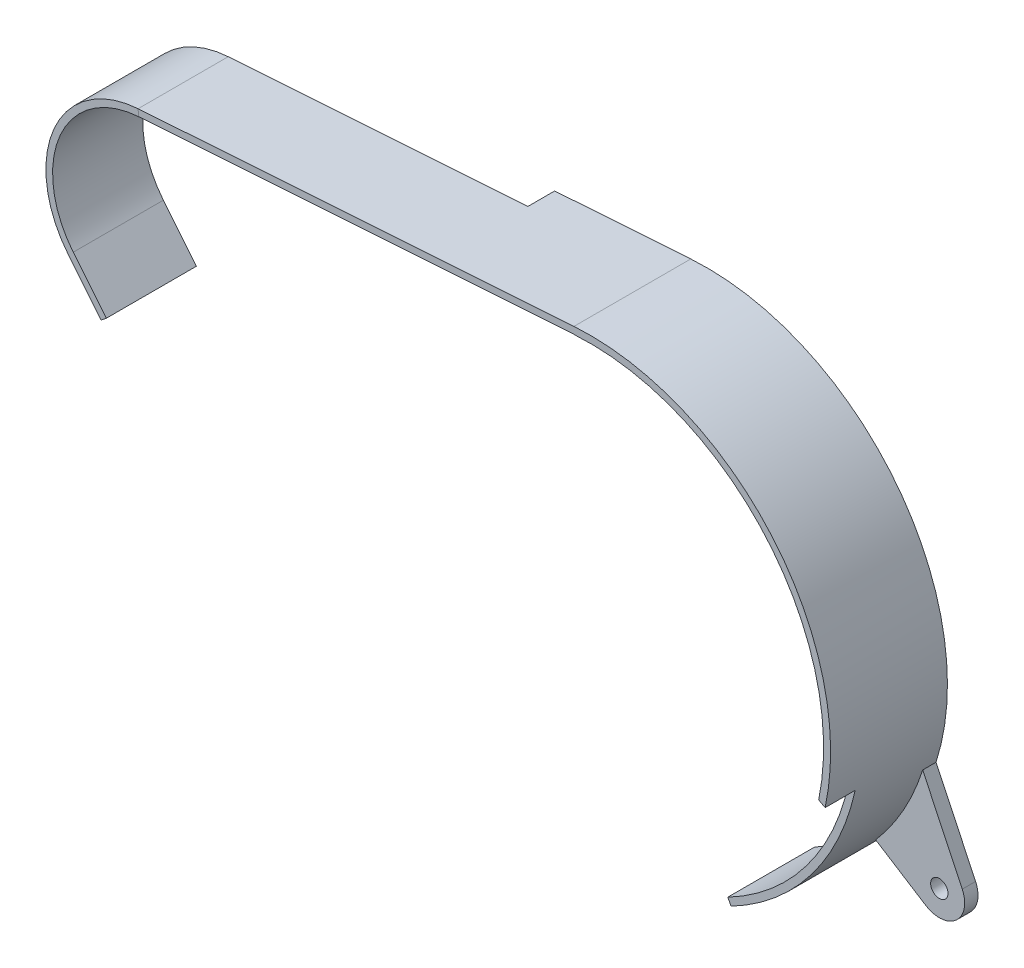
SolidWorks part; units mm, degrees
ref_plane "Front Plane" through (0, 0, 0) normal (0, 0, 1) x (1, 0, 0)
ref_plane "Top Plane" through (0, 0, 0) normal (0, 1, 0) x (1, 0, 0)
ref_plane "Right Plane" through (0, 0, 0) normal (1, 0, 0) x (0, 0, -1)
sketch "Sketch1" plane through (0, 0, 0) normal (0, 0, 1) x (1, 0, 0)
  line L1 (0, -27.2415) -> (-46.2494, -27.2415) construction
  arc A0 (-2.3318, 34.9744) -> (-22.0577, -27.2415) centre (0, 0) ccw
  circle A2 centre (0, 0) radius 27.2415 construction
  dimension "D2" = 70.104
  dimension "D7" = 54.483
  dimension "D6" = 46.2494
  dimension "D9" = 65.2681
extrude "Extrude-Thin1" add sketch "Sketch1" along normal mid plane 44.45 thin thin type one direction wall 2.54
sketch "Sketch2" plane through (0, 0, 0) normal (0, 0, 1) x (1, 0, 0)
  line L2 (169.418, -121.539) -> (229.9374, -121.539) construction
  arc A1 (210.4449, -121.539) -> (163.5039, 46.0311) centre (169.418, -42.672) ccw
  circle A3 centre (169.418, -42.672) radius 78.867 construction
  dimension "D3" = 157.734
  dimension "D1" = 169.418
  dimension "D2" = 42.672
  dimension "D4" = 88.7031
  dimension "D5" = 88.9
  dimension "D6" = 60.5194
extrude "Extrude-Thin2" add sketch "Sketch2" along normal mid plane 44.45 separate body thin thin type one direction wall 2.667
sketch "Sketch4" plane through (0, 0, 0) normal (0, 0, 1) x (1, 0, 0)
  line L0 (-2.5008, 37.5087) -> (163.3265, 48.6922)
extrude "Extrude-Thin3" add sketch "Sketch4" along normal mid plane 44.45 thin thin type one direction wall 2.54
ref_plane "Plane1" through (163.3265, 48.6922, 22.225) normal (-0.9978, -0.0665, 0) x (0, 0, 1)
sketch "Sketch9" plane through (0, 0, 22.225) normal (0, 0, 1) x (1, 0, 0)
  line L0 (210.4449, -121.539) -> (211.6757, -123.905)
  line L1 (258.8971, -62.1142) -> (256.4512, -60.7948)
  arc A0 (210.4449, -121.539) -> (256.4512, -60.7948) centre (169.418, -42.672) ccw
  arc A1 (210.4449, -121.539) -> (163.5039, 46.0311) centre (169.418, -42.672) ccw construction
  arc A2 (211.6757, -123.905) -> (258.8971, -62.1142) centre (169.418, -42.672) ccw
  arc A3 (211.6757, -123.905) -> (163.3265, 48.6922) centre (169.418, -42.672) ccw construction
  dimension "D1" = 88.9
  dimension "D2" = 76.2
  dimension "D3" = 2.7791
extrude "Cut-Extrude2" cut sketch "Sketch9" against normal blind 11.43
sketch "Sketch11" plane through (0, 0, -22.225) normal (0, 0, -1) x (-1, 0, 0)
  line L0 (-271.6994, -102.2461) -> (-256.6552, -70.4961)
  line L1 (-257.8131, -114.5335) -> (-238.7631, -102.4698)
  arc A0 (-271.6994, -102.2461) -> (-257.8131, -114.5335) centre (-262.977, -106.379) ccw
  circle A1 centre (-262.977, -106.379) radius 3.302
  arc A2 (-163.3265, 48.6922) -> (-211.6757, -123.905) centre (-169.418, -42.672) ccw construction
  arc A3 (-256.6552, -70.4961) -> (-238.7631, -102.4698) centre (-169.418, -42.672) ccw
  dimension "D1" = 19.304
  dimension "D2" = 6.604
  dimension "D6" = 91.567
  dimension "D3" = 17.526
  dimension "D4" = 51.3013
  dimension "D5" = 31.75
  dimension "D7" = 19.05
extrude "Boss-Extrude1" add sketch "Sketch11" against normal blind 5.08
sketch "Sketch17" plane through (0, 0, 22.225) normal (0, 0, 1) x (1, 0, 0)
  line L0 (0, 0) -> (-29.1599, -23.7247) construction
  line L1 (-29.1599, -23.7247) -> (-27.1896, -22.1216)
  line L2 (-27.1896, -22.1216) -> (-22.0577, -27.2415)
  line L3 (-22.0577, -27.2415) -> (-23.6561, -29.2155)
  arc A0 (-2.3318, 34.9744) -> (-22.0577, -27.2415) centre (0, 0) ccw construction
  arc A1 (-23.6561, -29.2155) -> (-29.1599, -23.7247) centre (0, 0) cw
  dimension "D1" = 37.592
  dimension "D2" = 58.6991
extrude "Cut-Extrude5" cut sketch "Sketch17" against normal through all
sketch "Sketch18" plane through (0, 0, 22.225) normal (0, 0, 1) x (1, 0, 0)
  line L0 (-42.8922, -37.592) -> (37.592, -37.592) construction
  line L1 (-29.1599, -23.7247) -> (-16.5731, -39.195)
  line L2 (-27.1896, -22.1216) -> (-14.6028, -37.592)
  line L3 (-16.5731, -39.195) -> (-14.6028, -37.592)
  line L6 (-29.1599, -23.7247) -> (-27.1896, -22.1216)
  line L7 (-2.3318, 34.9744) -> (-2.5008, 37.5087)
  line L9 (-2.3318, 34.9744) -> (-2.5008, 37.5087)
  circle A0 centre (0, 0) radius 37.592 construction
  arc A3 (-2.3318, 34.9744) -> (-27.1896, -22.1216) centre (0, 0) ccw
  arc A4 (-2.5008, 37.5087) -> (-29.1599, -23.7247) centre (0, 0) ccw
  arc A5 (-2.3318, 34.9744) -> (-27.1896, -22.1216) centre (0, 0) ccw
  arc A6 (-2.5008, 37.5087) -> (-29.1599, -23.7247) centre (0, 0) ccw
  dimension "D1" = 75.184
  dimension "D2" = 0
extrude "Boss-Extrude5" add sketch "Sketch18" against normal through all
sketch "Sketch19" plane through (-2.5295, 37.5068, 0) normal (-0.0673, 0.9977, 0) x (0.9977, 0.0673, 0)
  line L0 (-37.592, 22.225) -> (-37.592, -22.225) construction
  line L1 (-37.592, 22.225) -> (114.3287, 22.225)
  line L2 (-37.592, 22.225) -> (-37.592, 12.065)
  line L3 (-37.592, 12.065) -> (114.3287, 12.065)
  line L4 (114.3287, 22.225) -> (114.3287, 12.065)
  line L5 (0.0287, 22.225) -> (166.2327, 22.225) construction
  dimension "D1" = 10.16
  dimension "D2" = 114.3
extrude "Cut-Extrude7" cut sketch "Sketch19" against normal through all
